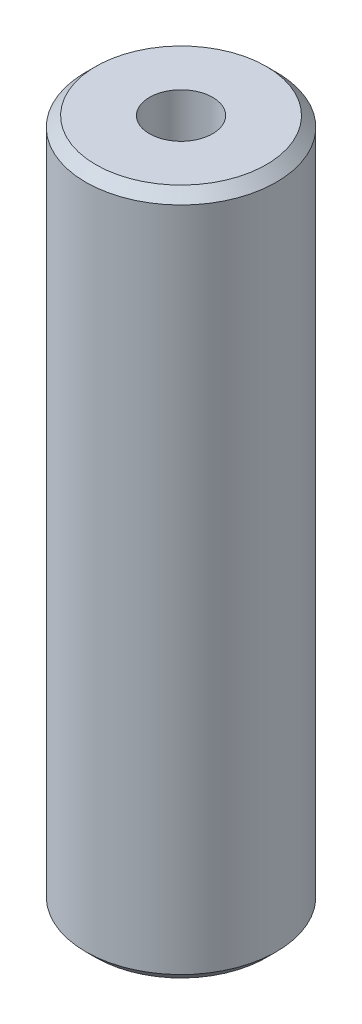
SolidWorks part; units mm, degrees
ref_plane "Front Plane" through (0, 0, 0) normal (0, 0, 1) x (1, 0, 0)
ref_plane "Top Plane" through (0, 0, 0) normal (0, 1, 0) x (1, 0, 0)
ref_plane "Right Plane" through (0, 0, 0) normal (1, 0, 0) x (0, 0, -1)
sketch "Sketch1" plane through (0, 0, 0) normal (0, 1, 0) x (1, 0, 0)
  circle A0 centre (0, 0) radius 15
  dimension "SHAFT_OD" = 30
extrude "Boss-Extrude1" add sketch "Sketch1" along normal blind 108.0712
sketch "Sketch2" plane through (0, 0, 0) normal (0, 1, 0) x (1, 0, 0)
  circle A0 centre (0, 0) radius 4.9714
  dimension "BORE_D" = 9.9429
extrude "Cut-Extrude1" cut sketch "Sketch2" along normal through all
chamfer "Chamfer1" distance 1.5913 angle 45 2 edges at (0, 108.0712, 15) (0, 0, 15)
